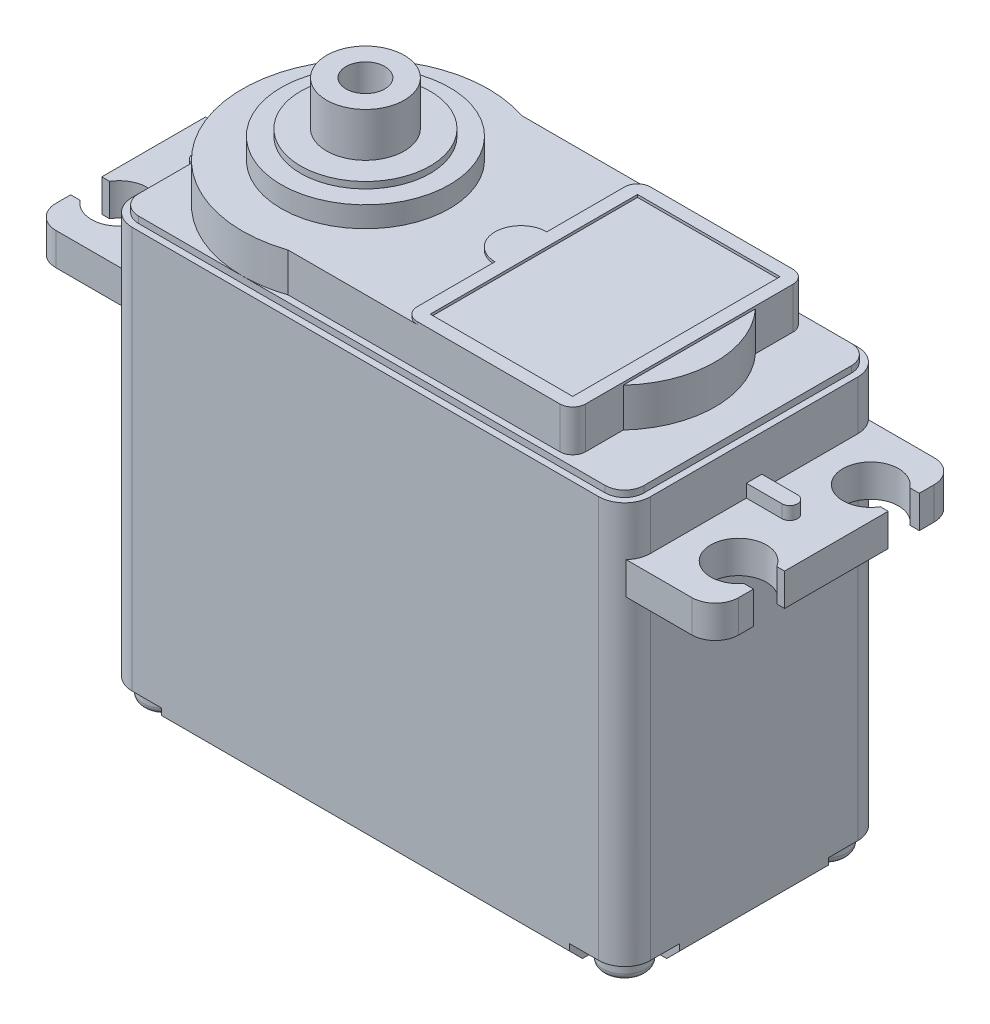
SolidWorks part; units mm, degrees
ref_plane "Спереди" through (0, 0, 0) normal (0, 0, 1) x (1, 0, 0)
ref_plane "Сверху" through (0, 0, 0) normal (0, 1, 0) x (1, 0, 0)
ref_plane "Справа" through (0, 0, 0) normal (1, 0, 0) x (0, 0, -1)
sketch "Эскиз1" plane through (0, 0, 0) normal (0, 1, 0) x (1, 0, 0)
  line L1 (-18, -10) -> (18, -10)
  line L2 (-20, -8) -> (-20, 8)
  line L3 (-18, 10) -> (18, 10)
  line L4 (20, -8) -> (20, 8)
  line L5 (-20, -10) -> (20, 10) construction
  line L6 (-20, 10) -> (20, -10) construction
  arc A0 (-18, -10) -> (-20, -8) centre (-18, -8) cw
  arc A1 (20, -8) -> (18, -10) centre (18, -8) cw
  arc A2 (20, 8) -> (18, 10) centre (18, 8) ccw
  arc A3 (-20, 8) -> (-18, 10) centre (-18, 8) cw
  point P0 (0, 0)
  dimension "D3" = 2
  dimension "D1" = 20
  dimension "D2" = 40
extrude "Бобышка-Вытянуть1" add sketch "Эскиз1" along normal blind 32.5
sketch "Эскиз2" plane through (0, 32.5, 0) normal (0, 1, 0) x (1, 0, 0)
  line L12 (-18, -9.5) -> (18, -9.5)
  line L13 (19.5, -8) -> (19.5, 8)
  line L14 (18, 9.5) -> (-18, 9.5)
  line L15 (-19.5, 8) -> (-19.5, -8)
  line L16 (-18, -9.5) -> (18, -9.5)
  line L17 (19.5, -8) -> (19.5, 8)
  line L18 (18, 9.5) -> (-18, 9.5)
  line L19 (-19.5, 8) -> (-19.5, -8)
  arc A10 (-19.5, -8) -> (-18, -9.5) centre (-18, -8) ccw
  arc A11 (18, -9.5) -> (19.5, -8) centre (18, -8) ccw
  arc A12 (19.5, 8) -> (18, 9.5) centre (18, 8) ccw
  arc A13 (-18, 9.5) -> (-19.5, 8) centre (-18, 8) ccw
  arc A14 (-19.5, -8) -> (-18, -9.5) centre (-18, -8) ccw
  arc A15 (18, -9.5) -> (19.5, -8) centre (18, -8) ccw
  arc A16 (19.5, 8) -> (18, 9.5) centre (18, 8) ccw
  arc A17 (-18, 9.5) -> (-19.5, 8) centre (-18, 8) ccw
  dimension "D1" = 0.5
extrude "Бобышка-Вытянуть2" add sketch "Эскиз2" along normal blind 0.5
sketch "Эскиз3" plane through (0, 0, 0) normal (0, -1, 0) x (1, 0, 0)
  line L0 (-21.9185, 5.75) -> (-17.75, 5.75)
  line L1 (-15.75, 7.75) -> (-15.75, 12.0926)
  line L2 (-20, -8) -> (-20, 8) construction
  line L3 (-18, 10) -> (18, 10) construction
  line L4 (-21.9185, 5.75) -> (-21.9185, 12.0926)
  line L6 (-15.75, 12.0926) -> (-21.9185, 12.0926)
  line L8 (15.75, 12.0926) -> (21.9185, 12.0926)
  line L9 (21.9185, 5.75) -> (21.9185, 12.0926)
  line L10 (15.75, 7.75) -> (15.75, 12.0926)
  line L11 (21.9185, 5.75) -> (17.75, 5.75)
  line L12 (21.9185, -5.75) -> (17.75, -5.75)
  line L13 (15.75, -7.75) -> (15.75, -12.0926)
  line L14 (21.9185, -5.75) -> (21.9185, -12.0926)
  line L15 (15.75, -12.0926) -> (21.9185, -12.0926)
  line L16 (-15.75, -12.0926) -> (-21.9185, -12.0926)
  line L17 (-21.9185, -5.75) -> (-21.9185, -12.0926)
  line L18 (-15.75, -7.75) -> (-15.75, -12.0926)
  line L19 (-21.9185, -5.75) -> (-17.75, -5.75)
  arc A0 (-15.75, 7.75) -> (-17.75, 5.75) centre (-17.75, 7.75) cw
  arc A1 (15.75, 7.75) -> (17.75, 5.75) centre (17.75, 7.75) ccw
  arc A2 (15.75, -7.75) -> (17.75, -5.75) centre (17.75, -7.75) cw
  arc A3 (-15.75, -7.75) -> (-17.75, -5.75) centre (-17.75, -7.75) ccw
  point P11 (-15.75, 5.75)
  point P21 (15.75, 5.75)
  point P34 (15.75, -5.75)
  point P35 (-15.75, -5.75)
  dimension "D3" = 2
  dimension "D1" = 4.25
  dimension "D2" = 4.25
extrude "Вырез-Вытянуть1" cut sketch "Эскиз3" against normal blind 1.5
chamfer "Фаска1" distance 1 angle 45 4 edges at (20, 0, 0) (0, 0, -10) (-20, 0, 0) (0, 0, 10)
sketch "Эскиз4" plane through (0, 33, 0) normal (0, 1, 0) x (1, 0, 0)
  line L1 (18, 9.5) -> (-18, 9.5) construction
  line L2 (-18, -9.5) -> (18, -9.5) construction
  line L3 (-19.5, 8) -> (-19.5, -8) construction
  line L4 (15, 8) -> (15, -8)
  line L5 (20, -8) -> (20, 8) construction
  line L6 (-6.9586, 9) -> (14, 9)
  line L7 (-6.9586, -9) -> (14, -9)
  line L8 (18, 10) -> (-18, 10) construction
  line L9 (-18, -10) -> (18, -10) construction
  arc A0 (-6.9586, 9) -> (-6.9586, -9) centre (-10, 0) ccw
  arc A1 (15, 8) -> (14, 9) centre (14, 8) ccw
  arc A2 (15, -8) -> (14, -9) centre (14, -8) cw
  dimension "D1" = 5
  dimension "D4" = 1
  dimension "D2" = 1
  dimension "D3" = 1
extrude "Бобышка-Вытянуть3" add sketch "Эскиз4" along normal blind 3
sketch "Эскиз5" plane through (0, 36, 0) normal (0, 1, 0) x (1, 0, 0)
  line L0 (15, -8) -> (15, 8) construction
  line L1 (15, -8) -> (15, 8)
  line L2 (2, 8) -> (2, 2)
  line L3 (14, 9) -> (3, 9)
  line L4 (2, -2) -> (2, -8)
  line L5 (14, -9) -> (3, -9)
  line L6 (3, -8) -> (14, -8)
  line L7 (14, 8) -> (3, 8)
  line L8 (3, 8) -> (3, -8)
  line L9 (14, -8) -> (14, 8)
  line L11 (2, 8) -> (2, -8) construction
  arc A0 (15, 8) -> (14, 9) centre (14, 8) ccw construction
  arc A1 (14, -9) -> (15, -8) centre (14, -8) ccw construction
  arc A2 (15, 8) -> (14, 9) centre (14, 8) ccw
  arc A3 (14, -9) -> (15, -8) centre (14, -8) ccw
  arc A4 (3, -9) -> (2, -8) centre (3, -8) cw
  arc A5 (3, 9) -> (2, 8) centre (3, 8) ccw
  arc A6 (2, 2) -> (2, -2) centre (2, 0) ccw
  arc M1 (15, 8) -> (14, 9) centre (14, 8) ccw
  line M2 (14, 9) -> (-6.9586, 9)
  line M4 (-6.9586, -9) -> (14, -9)
  arc M5 (14, -9) -> (15, -8) centre (14, -8) ccw
  line M6 (15, -8) -> (15, 8)
  dimension "D2" = 1
  dimension "D4" = 4
  dimension "D1" = 13
  dimension "D3" = 1
extrude "Бобышка-Вытянуть4" add sketch "Эскиз5" along normal blind 0.2 contours L11 A6 | L2 L11 L4 A4 A5 L9 L6 L8 L7 M4 M5 M6 M1 M2 region at (14.5501, 36, 8.5501) region at (1.1512, 36, 0)
sketch "Эскиз6" plane through (0, 36, 0) normal (0, 1, 0) x (1, 0, 0)
  circle A0 centre (-10, 0) radius 6.5
  dimension "D1" = 13
extrude "Бобышка-Вытянуть5" add sketch "Эскиз6" along normal blind 1.6
sketch "Эскиз7" plane through (0, 37.6, 0) normal (0, 1, 0) x (1, 0, 0)
  circle A0 centre (-10, 0) radius 5
  dimension "D1" = 10
extrude "Бобышка-Вытянуть6" add sketch "Эскиз7" along normal blind 0.5
sketch "Эскиз8" plane through (0, 38.1, 0) normal (0, 1, 0) x (1, 0, 0)
  circle A0 centre (-10, 0) radius 3
  circle A1 centre (-10, 0) radius 1.5
  dimension "D1" = 6
  dimension "D2" = 3
extrude "Бобышка-Вытянуть7" add sketch "Эскиз8" along normal blind 3.4
sketch "Эскиз9" plane through (0, 33, 0) normal (0, 1, 0) x (1, 0, 0)
  line L1 (20, -8) -> (20, 8) construction
  line L2 (14.5, 5.5902) -> (14.5, -5.5902)
  line L3 (19.5, -8) -> (19.5, 8) construction
  arc A0 (14.5, -5.5902) -> (14.5, 5.5902) centre (9.5, 0) ccw
  dimension "D1" = 15
  dimension "D2" = 10.5
  dimension "D3" = 5
extrude "Бобышка-Вытянуть8" add sketch "Эскиз9" along normal blind 3
ref_plane "Плоскость1" through (0, 26.5, 0) normal (0, -1, 0) x (-1, 0, 0)
sketch "Эскиз10" plane through (0, 26.5, 0) normal (0, -1, 0) x (-1, 0, 0)
  line L0 (-26.35, 6.4) -> (-25.6125, 6.4)
  line L1 (-24.5384, -9.35) -> (24.5384, -9.35)
  line L2 (-26.35, -7.5384) -> (-26.35, -6.4)
  line L3 (-24.5384, 9.35) -> (24.5384, 9.35)
  line L4 (26.35, -7.5384) -> (26.35, -6.4)
  line L5 (-26.35, -9.35) -> (26.35, 9.35) construction
  line L6 (-26.35, 9.35) -> (26.35, -9.35) construction
  line L7 (-26.35, 4) -> (-25.7473, 4)
  line L8 (-26.35, 6.4) -> (-26.35, 7.5384)
  line L9 (0, 0) -> (-7.7074, 0) construction
  line L10 (-7.7074, 0) -> (0, 0) construction
  line L11 (0, 0) -> (0, 4.5311) construction
  line L12 (26.35, 4) -> (25.7473, 4)
  line L13 (26.35, 6.4) -> (25.6125, 6.4)
  line L14 (26.35, 6.4) -> (26.35, 7.5384)
  line L15 (26.35, -4) -> (25.7473, -4)
  line L16 (26.35, -6.4) -> (25.6125, -6.4)
  line L17 (-26.35, -4) -> (-25.7473, -4)
  line L18 (-26.35, -6.4) -> (-25.6125, -6.4)
  line L19 (26.35, -4) -> (26.35, 4)
  line L20 (-26.35, -4) -> (-26.35, 4)
  arc A0 (26.35, 7.5384) -> (24.5384, 9.35) centre (24.5384, 7.5384) ccw
  arc A1 (26.35, -7.5384) -> (24.5384, -9.35) centre (24.5384, -7.5384) cw
  arc A2 (-24.5384, -9.35) -> (-26.35, -7.5384) centre (-24.5384, -7.5384) cw
  arc A3 (-26.35, 7.5384) -> (-24.5384, 9.35) centre (-24.5384, 7.5384) cw
  arc A4 (-25.7473, 4) -> (-25.6125, 6.4) centre (-23.9, 5.1) ccw
  arc A5 (25.7473, 4) -> (25.6125, 6.4) centre (23.9, 5.1) cw
  arc A6 (25.7473, -4) -> (25.6125, -6.4) centre (23.9, -5.1) ccw
  arc A7 (-25.7473, -4) -> (-25.6125, -6.4) centre (-23.9, -5.1) cw
  point P0 (0, 0)
  dimension "D3" = 1.8116
  dimension "D4" = 4.3
  dimension "D1" = 18.7
  dimension "D2" = 52.7
  dimension "D5" = 5.1
  dimension "D6" = 23.9
  dimension "D7" = 1.3
  dimension "D8" = 2.4
extrude "Бобышка-Вытянуть9" add sketch "Эскиз10" against normal blind 2.5 from offset 0.3
sketch "Эскиз11" plane through (0, 28.7, 0) normal (0, 1, 0) x (1, 0, 0)
  line L0 (26.35, 4) -> (26.35, -4) construction
  line L1 (22.75, 0.6) -> (18.0276, 0.6)
  line L2 (22.75, -0.6) -> (18.0276, -0.6)
  line L6 (18.0276, -0.6) -> (18.0276, 0.6)
  line L7 (0, 0) -> (0, 3.7247) construction
  line L8 (-22.75, 0.6) -> (-18.0276, 0.6)
  line L9 (-18.0276, -0.6) -> (-18.0276, 0.6)
  line L10 (-22.75, -0.6) -> (-18.0276, -0.6)
  arc A0 (22.75, -0.6) -> (22.75, 0.6) centre (22.75, 0) ccw
  arc A1 (2, 2) -> (2, -2) centre (2, 0) ccw construction
  arc A2 (-22.75, -0.6) -> (-22.75, 0.6) centre (-22.75, 0) cw
  point P4 (26.35, 0)
  dimension "D1" = 1.2
  dimension "D2" = 3.6
extrude "Бобышка-Вытянуть10" add sketch "Эскиз11" along normal blind 1
sketch "Эскиз12" plane through (0, 1.5, 0) normal (0, -1, 0) x (1, 0, 0)
  line L0 (0, 0) -> (0, 4.3916) construction
  line L1 (0, 0) -> (-4.3775, 0) construction
  line L2 (-18, 8) -> (-19, 8)
  line L3 (-19, 8) -> (-19, 7.5)
  line L4 (-19, 7.5) -> (-18, 7.5)
  line L5 (-17.5, 8) -> (-17.5, 9)
  line L6 (-17.5, 9) -> (-18, 9)
  line L7 (-18, 9) -> (-18, 8)
  line L8 (-17.5, 7.5) -> (-16.5, 7.5)
  line L9 (-16.5, 7.5) -> (-16.5, 8)
  line L10 (-16.5, 8) -> (-17.5, 8)
  line L11 (-18, 7.5) -> (-18, 6.5)
  line L12 (-18, 6.5) -> (-17.5, 6.5)
  line L13 (-17.5, 6.5) -> (-17.5, 7.5)
  line L14 (16.5, 7.5) -> (16.5, 8)
  line L15 (17.5, 7.5) -> (16.5, 7.5)
  line L16 (17.5, 6.5) -> (17.5, 7.5)
  line L17 (18, 6.5) -> (17.5, 6.5)
  line L18 (18, 7.5) -> (18, 6.5)
  line L19 (19, 7.5) -> (18, 7.5)
  line L20 (19, 8) -> (19, 7.5)
  line L21 (18, 8) -> (19, 8)
  line L22 (18, 9) -> (18, 8)
  line L23 (17.5, 9) -> (18, 9)
  line L24 (17.5, 8) -> (17.5, 9)
  line L25 (16.5, 8) -> (17.5, 8)
  line L26 (16.5, -8) -> (17.5, -8)
  line L27 (16.5, -7.5) -> (16.5, -8)
  line L28 (17.5, -7.5) -> (16.5, -7.5)
  line L29 (18, -6.5) -> (17.5, -6.5)
  line L30 (17.5, -6.5) -> (17.5, -7.5)
  line L31 (18, -7.5) -> (18, -6.5)
  line L32 (19, -7.5) -> (18, -7.5)
  line L33 (19, -8) -> (19, -7.5)
  line L34 (18, -8) -> (19, -8)
  line L35 (18, -9) -> (18, -8)
  line L36 (17.5, -9) -> (18, -9)
  line L37 (17.5, -8) -> (17.5, -9)
  line L38 (-17.5, -6.5) -> (-17.5, -7.5)
  line L39 (-18, -6.5) -> (-17.5, -6.5)
  line L40 (-18, -7.5) -> (-18, -6.5)
  line L41 (-19, -7.5) -> (-18, -7.5)
  line L42 (-19, -8) -> (-19, -7.5)
  line L43 (-18, -8) -> (-19, -8)
  line L44 (-16.5, -7.5) -> (-16.5, -8)
  line L45 (-17.5, -7.5) -> (-16.5, -7.5)
  line L46 (-16.5, -8) -> (-17.5, -8)
  line L47 (-17.5, -8) -> (-17.5, -9)
  line L48 (-18, -9) -> (-18, -8)
  line L49 (-17.5, -9) -> (-18, -9)
  circle A0 centre (-17.75, 7.75) radius 1.65
  circle A1 centre (17.75, 7.75) radius 1.65
  circle A2 centre (17.75, -7.75) radius 1.65
  circle A3 centre (-17.75, -7.75) radius 1.65
  dimension "D1" = 3.3
  dimension "D2" = 7.75
  dimension "D3" = 17.75
  dimension "D4" = 0.5
  dimension "D5" = 0.25
  dimension "D6" = 1.25
  dimension "D7" = 4
extrude "Бобышка-Вытянуть11" add sketch "Эскиз12" along normal blind 1.5
fillet "Скругление1" radius 0.5 4 edges at (17.75, 0, 9.4) (17.75, 0, -9.4) (-17.75, 0, -6.1) (-17.75, 0, 6.1)
sketch "스케치1" plane through (0, 0, 0) normal (1, 0, 0) x (0, 0, -1)
  line L0 (5.75, 0) -> (-5.75, 0) construction
  line L1 (-3.5, 6) -> (3.5, 6)
  line L2 (-3.5, 6) -> (-3.5, 0)
  line L3 (-3.5, 0) -> (3.5, 0)
  line L4 (3.5, 6) -> (3.5, 0)
  line L5 (-3.5, 6) -> (3.5, 0) construction
  line L6 (-3.5, 0) -> (3.5, 6) construction
  line L7 (-3.5, 1) -> (3.5, 1)
  line L8 (-5.75, 1) -> (5.75, 1) construction
  point P0 (0, 3)
  dimension "D1" = 7
  dimension "D3" = 6
extrude "보스-돌출1" add sketch "스케치1" against normal blind 22.5 contours L2 L7 L4 L1 region at (0, 3.5, 0)
